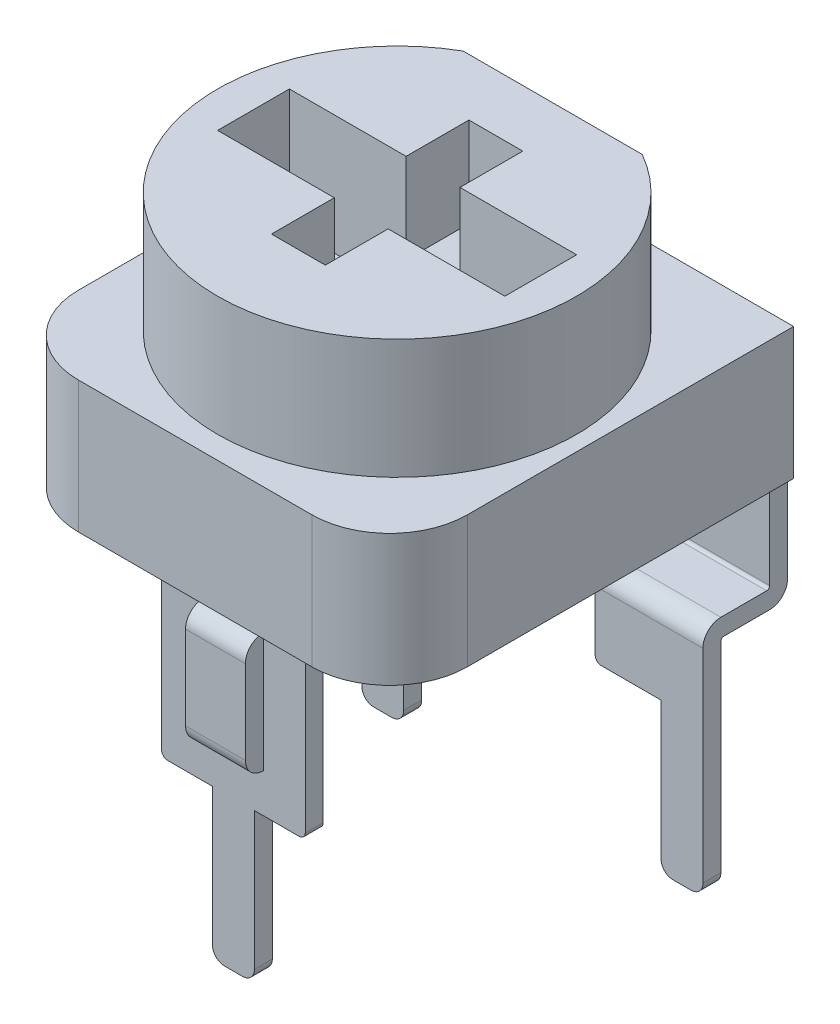
SolidWorks part; units mm, degrees
material "PVC Rigid"
ref_plane "Front Plane" through (0, 0, 0) normal (0, 0, 1) x (1, 0, 0)
ref_plane "Top Plane" through (0, 0, 0) normal (0, 1, 0) x (1, 0, 0)
ref_plane "Right Plane" through (0, 0, 0) normal (1, 0, 0) x (0, 0, -1)
sketch "Sketch1" plane through (0, 0, 0) normal (0, 1, 0) x (1, 0, 0)
  line L0 (-1.4967, 2.6) -> (1.4967, 2.6)
  arc A0 (-1.4967, 2.6) -> (1.4967, 2.6) centre (0, 0) ccw
  dimension "D1" = 6
  dimension "D2" = 2.6
extrude "Boss-Extrude1" add sketch "Sketch1" along normal blind 2
sketch "Sketch2" plane through (0, 2, 0) normal (0, 1, 0) x (1, 0, 0)
  line L1 (-2.4, -0.6) -> (2.4, -0.6)
  line L2 (-2.4, -0.6) -> (-2.4, 0.6)
  line L3 (-2.4, 0.6) -> (2.4, 0.6)
  line L4 (2.4, -0.6) -> (2.4, 0.6)
  line L5 (-2.4, -0.6) -> (2.4, 0.6) construction
  line L6 (-2.4, 0.6) -> (2.4, -0.6) construction
  point P0 (0, 0)
  point P6 (0, 0)
  dimension "D1" = 1.2
  dimension "D2" = 4.8
extrude "Cut-Extrude1" cut sketch "Sketch2" against normal through all
sketch "Sketch3" plane through (0, 2, 0) normal (0, 1, 0) x (1, 0, 0)
  line L1 (-0.45, -1.65) -> (0.45, -1.65)
  line L2 (-0.45, -1.65) -> (-0.45, 1.65)
  line L3 (-0.45, 1.65) -> (0.45, 1.65)
  line L4 (0.45, -1.65) -> (0.45, 1.65)
  line L5 (-0.45, -1.65) -> (0.45, 1.65) construction
  line L6 (-0.45, 1.65) -> (0.45, -1.65) construction
  point P0 (0, 0)
  dimension "D1" = 0.9
  dimension "D2" = 3.3
extrude "Cut-Extrude2" cut sketch "Sketch3" against normal blind 1.5
sketch "Sketch4" plane through (0, 0, 0) normal (0, -1, 0) x (1, 0, 0)
  line L1 (-3.25, -3.375) -> (3.25, -3.375)
  line L2 (-3.25, -3.375) -> (-3.25, 2.075)
  line L3 (-1.95, 3.375) -> (1.95, 3.375)
  line L4 (3.25, -3.375) -> (3.25, 2.075)
  line L5 (-3.25, -3.375) -> (2.8764, 2.987) construction
  line L6 (-2.8764, 2.987) -> (3.25, -3.375) construction
  arc A0 (-1.95, 3.375) -> (-3.25, 2.075) centre (-1.95, 2.075) ccw
  arc A1 (3.25, 2.075) -> (1.95, 3.375) centre (1.95, 2.075) ccw
  point P0 (0, 0)
  dimension "D3" = 1.95
  dimension "D4" = 6.5
  dimension "D1" = 2.6
  dimension "D2" = 2.075
  dimension "D5" = 3.375
extrude "Boss-Extrude2" add sketch "Sketch4" along normal blind 2.2 separate body
sketch "Sketch5" plane through (0, -2.2, 0) normal (0, -1, 0) x (1, 0, 0)
  line L1 (-1.2, 2.735) -> (1.2, 2.735)
  line L2 (-1.2, 2.735) -> (-1.2, 2.435)
  line L3 (-1.2, 2.435) -> (1.2, 2.435)
  line L4 (1.2, 2.735) -> (1.2, 2.435)
  line L5 (-1.2, 2.735) -> (1.2, 2.435) construction
  line L6 (-1.2, 2.435) -> (1.2, 2.735) construction
  point P0 (0, 2.585)
  dimension "D1" = 0.3
  dimension "D2" = 2.4
  dimension "D3" = 2.585
  dimension "D4" = 1.2
extrude "Boss-Extrude3" add sketch "Sketch5" along normal blind 3.2 separate body
sketch "Sketch6" plane through (0, -5.4, 0) normal (0, -1, 0) x (1, 0, 0)
  line L1 (-0.35, 2.435) -> (0.35, 2.435)
  line L2 (-0.35, 2.435) -> (-0.35, 2.735)
  line L3 (-0.35, 2.735) -> (0.35, 2.735)
  line L4 (0.35, 2.435) -> (0.35, 2.735)
  line L5 (-0.35, 2.435) -> (0.35, 2.735) construction
  line L6 (-0.35, 2.735) -> (0.35, 2.435) construction
  line L7 (1.2, 2.435) -> (1.2, 2.735) construction
  line L8 (1.2, 2.735) -> (-1.2, 2.735) construction
  point P0 (0, 2.585)
  dimension "D1" = 0.3
  dimension "D2" = 0.7
  dimension "D3" = 1.2
  dimension "D4" = 0.15
extrude "Boss-Extrude4" add sketch "Sketch6" along normal blind 2.5
fillet "Fillet1" radius 0.1 2 edges at (-1.2, -5.4, 2.585) (1.2, -5.4, 2.585)
fillet "Fillet2" radius 0.2 2 edges at (0.35, -7.9, 2.585) (-0.35, -7.9, 2.585)
sketch "Sketch8" plane through (0, 0, 2.735) normal (0, 0, 1) x (1, 0, 0)
  line L2 (-0.5, -2.75) -> (0.5, -2.75)
  line L3 (-0.5, -2.75) -> (-0.5, -4.75)
  line L4 (-0.5, -4.75) -> (0.5, -4.75)
  line L5 (0.5, -2.75) -> (0.5, -4.75)
  line L6 (-0.5, -2.75) -> (0.5, -4.75) construction
  line L8 (0, -2.2) -> (0, -8.9171) construction
  line L9 (-1.2, -3.75) -> (1.2, -3.75) construction
  line L10 (-1.2, -5.3) -> (-1.2, -2.2) construction
  line L11 (1.2, -5.3) -> (1.2, -2.2) construction
  line L12 (-0.5, -4.75) -> (0.5, -2.75) construction
  point P0 (0, -3.75)
  dimension "D1" = 1
  dimension "D2" = 2
extrude "Boss-Extrude5" add sketch "Sketch8" along normal blind 0.3
fillet "Fillet3" radius 0.3 2 edges at (0, -4.75, 3.035) (0, -2.75, 3.035)
sketch "Sketch16" plane through (0, 0, 2.435) normal (0, 0, -1) x (-1, 0, 0)
  line L0 (-0.4, -3.05) -> (0.4, -3.05)
  line L1 (-0.4, -3.05) -> (-0.4, -4.45)
  line L2 (-0.4, -4.45) -> (0.4, -4.45)
  line L3 (0.4, -3.05) -> (0.4, -4.45)
  line L4 (-0.4, -3.05) -> (0.4, -4.45) construction
  line L5 (0, -2.2) -> (0, -5.026) construction
  line L6 (1.2, -2.2) -> (-1.2, -2.2) construction
  line L7 (-0.4, -4.45) -> (0.4, -3.05) construction
  line L8 (-1.2, -3.75) -> (1.2, -3.75) construction
  line L9 (-1.2, -5.3) -> (-1.2, -2.2) construction
  line L10 (1.2, -5.3) -> (1.2, -2.2) construction
  point P0 (0, -3.75)
  dimension "D1" = 0.8
  dimension "D2" = 1.4
extrude "Cut-Extrude5" cut sketch "Sketch16" against normal blind 0.3
fillet "Fillet18" radius 0.3 2 edges at (0, -3.05, 2.735) (0, -4.45, 2.735)
sketch "Sketch9" plane through (0, 0, -3.375) normal (0, 0, -1) x (-1, 0, 0)
  line L1 (-2.85, -1) -> (-1.05, -1)
  line L2 (-2.85, -1) -> (-2.85, -4)
  line L3 (-2.85, -4) -> (-1.05, -4)
  line L4 (-1.05, -1) -> (-1.05, -4)
  line L5 (-2.85, -1) -> (-1.05, -4) construction
  line L6 (-2.85, -4) -> (-1.05, -1) construction
  line L9 (3.25, 0) -> (-3.25, 0) construction
  line L10 (0, 0) -> (0, -9.3004) construction
  line L11 (2.85, -1) -> (1.05, -4) construction
  line L12 (2.85, -4) -> (1.05, -1) construction
  line L13 (2.85, -4) -> (1.05, -4)
  line L14 (1.05, -1) -> (1.05, -4)
  line L15 (2.85, -1) -> (1.05, -1)
  line L16 (2.85, -1) -> (2.85, -4)
  point P0 (-1.95, -2.5)
  dimension "D1" = 1.8
  dimension "D2" = 3
  dimension "D3" = 1
  dimension "D4" = 2.1
extrude "Boss-Extrude6" add sketch "Sketch9" along normal blind 0.3 separate body
fillet "Fillet4" radius 0.3 1 edges at (1.95, -1, -3.675)
fillet "Fillet5" radius 0.3 1 edges at (-1.95, -1, -3.675)
sketch "Sketch10" plane through (0, -4, 0) normal (0, -1, 0) x (1, 0, 0)
  line L1 (-2.85, -3.675) -> (-1.05, -3.675)
  line L2 (-2.85, -3.675) -> (-2.85, -2.26)
  line L3 (-2.85, -2.26) -> (-1.05, -2.26)
  line L4 (-1.05, -3.675) -> (-1.05, -2.26)
  line L5 (1.05, -3.675) -> (2.85, -3.675)
  line L6 (1.05, -3.675) -> (1.05, -2.26)
  line L7 (1.05, -2.26) -> (2.85, -2.26)
  line L8 (2.85, -3.675) -> (2.85, -2.26)
  dimension "D1" = 1.415
  dimension "D2" = 1.8
  dimension "D3" = 1.415
  dimension "D4" = 1.8
extrude "Boss-Extrude7" add sketch "Sketch10" along normal blind 0.3
fillet "Fillet6" radius 0.3 1 edges at (-1.95, -4.3, -3.675)
fillet "Fillet7" radius 0.3 1 edges at (1.95, -4.3, -3.675)
fillet "Fillet8" radius 0.05 1 edges
fillet "Fillet9" radius 0.05 1 edges
sketch "Sketch11" plane through (0, -4.3, 0) normal (0, -1, 0) x (1, 0, 0)
  line L0 (-1.05, -3.375) -> (-1.05, -2.26) construction
  line L1 (-2.85, -2.26) -> (-1.05, -2.26)
  line L2 (-2.85, -2.26) -> (-2.85, -2.56)
  line L3 (-2.85, -2.56) -> (-1.05, -2.56)
  line L4 (-1.05, -2.26) -> (-1.05, -2.56)
  line L5 (0, -1.9185) -> (0, -4.5857) construction
  line L6 (1.05, -2.26) -> (1.05, -2.56)
  line L7 (2.85, -2.56) -> (1.05, -2.56)
  line L8 (2.85, -2.26) -> (2.85, -2.56)
  line L9 (2.85, -2.26) -> (1.05, -2.26)
  dimension "D1" = 0.3
extrude "Boss-Extrude8" add sketch "Sketch11" along normal blind 1.1
fillet "Fillet10" radius 0.3 1 edges at (-1.95, -4, -2.26)
fillet "Fillet11" radius 0.3 1 edges at (1.95, -4, -2.26)
fillet "Fillet12" radius 0.05 1 edges at (1.95, -4.3, -2.56)
fillet "Fillet13" radius 0.05 1 edges at (-1.95, -4.3, -2.56)
sketch "Sketch13" plane through (2.1208, -5.4, -5.8465) normal (0, -1, 0) x (1, 0, 0)
  line L0 (0.7292, 3.2865) -> (0.7292, 3.5865) construction
  line L1 (0.0292, 3.2865) -> (0.7292, 3.2865)
  line L2 (0.0292, 3.2865) -> (0.0292, 3.5865)
  line L3 (0.0292, 3.5865) -> (0.7292, 3.5865)
  line L4 (0.7292, 3.2865) -> (0.7292, 3.5865)
  line L5 (0.0292, 3.2865) -> (0.7292, 3.5865) construction
  line L6 (0.0292, 3.5865) -> (0.7292, 3.2865) construction
  line L7 (0.7292, 3.5865) -> (-1.0708, 3.5865) construction
  point P0 (0.3792, 3.4365)
  dimension "D1" = 0.3
  dimension "D2" = 0.7
  dimension "D3" = 0.35
  dimension "D4" = 0.15
extrude "Boss-Extrude9" add sketch "Sketch13" along normal blind 2.5
fillet "Fillet14" radius 0.2 2 edges at (2.85, -7.9, -2.41) (2.15, -7.9, -2.41)
sketch "Sketch15" plane through (-2.2614, -5.4, -5.8201) normal (0, -1, 0) x (1, 0, 0)
  line L0 (1.2114, 3.5601) -> (-0.5886, 3.5601) construction
  line L1 (-0.5886, 3.2601) -> (0.1114, 3.2601)
  line L2 (-0.5886, 3.2601) -> (-0.5886, 3.5601)
  line L3 (-0.5886, 3.5601) -> (0.1114, 3.5601)
  line L4 (0.1114, 3.2601) -> (0.1114, 3.5601)
  line L5 (-0.5886, 3.2601) -> (0.1114, 3.5601) construction
  line L6 (-0.5886, 3.5601) -> (0.1114, 3.2601) construction
  line L7 (-0.5886, 3.5601) -> (-0.5886, 3.2601) construction
  point P0 (-0.2386, 3.4101)
  dimension "D1" = 0.3
  dimension "D2" = 0.7
  dimension "D3" = 0.15
  dimension "D4" = 0.35
extrude "Boss-Extrude10" add sketch "Sketch15" along normal blind 2.5
fillet "Fillet15" radius 0.2 2 edges at (-2.15, -7.9, -2.41) (-2.85, -7.9, -2.41)
fillet "Fillet16" radius 0.1 1 edges at (1.05, -5.4, -2.41)
fillet "Fillet17" radius 0.1 1 edges at (-1.05, -5.4, -2.41)
